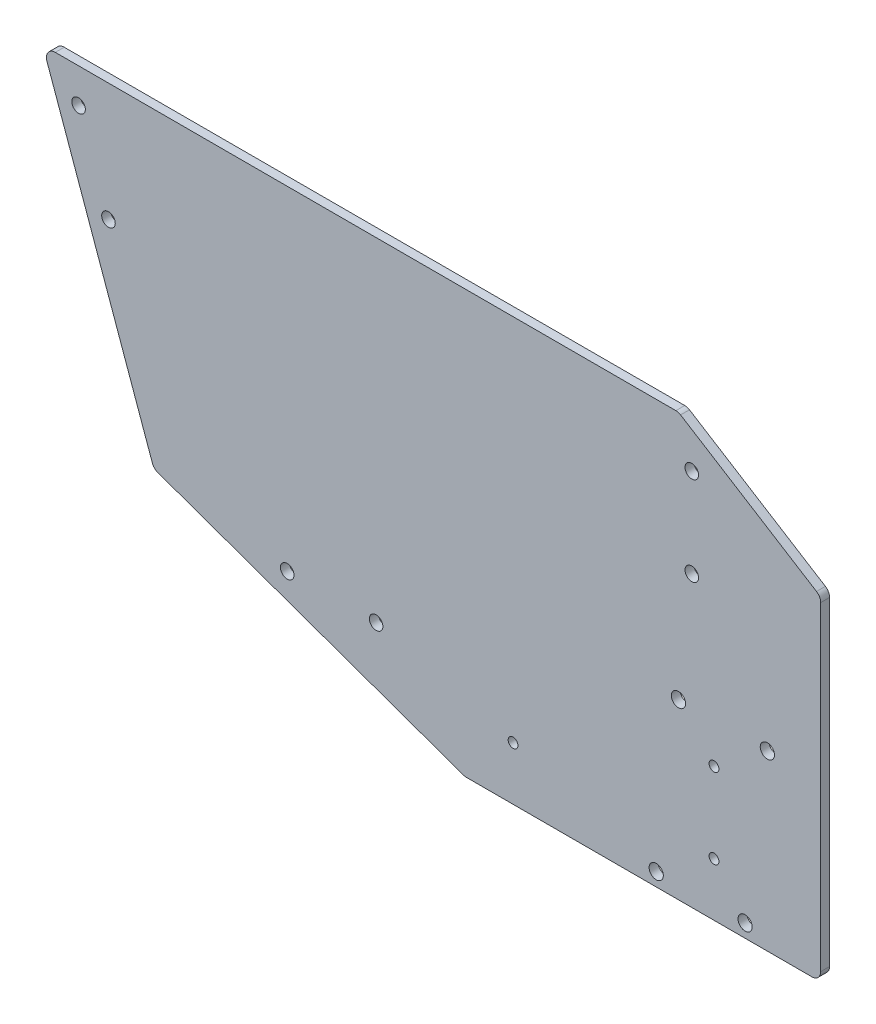
SolidWorks part; units mm, degrees
material "Thornel Mat VMA"
ref_plane "前视基准面" through (0, 0, 0) normal (0, 0, 1) x (1, 0, 0)
ref_plane "上视基准面" through (0, 0, 0) normal (0, 1, 0) x (1, 0, 0)
ref_plane "右视基准面" through (0, 0, 0) normal (1, 0, 0) x (0, 0, -1)
sketch "草图1" plane through (0, 0, 0) normal (0, 0, 1) x (1, 0, 0)
  line L0 (0, 0) -> (0, 75)
  line L1 (0, 75) -> (-32, 95)
  line L2 (-32, 95) -> (-175, 95)
  line L4 (-150, 25) -> (-80, 0)
  line L5 (-80, 0) -> (0, 0)
  line L6 (0, 3) -> (-17, 3) construction
  line L7 (-17, 3) -> (-37, 3) construction
  line L8 (-175, 95) -> (-150, 25)
  line L9 (-175, 95) -> (-170.2913, 96.6817) construction
  line L10 (-170.2913, 96.6817) -> (-166.9279, 87.2643) construction
  line L11 (-166.9279, 87.2643) -> (-160.2012, 68.4294) construction
  line L12 (-32, 95) -> (-29, 95) construction
  line L13 (-29, 95) -> (-29, 85) construction
  line L14 (-29, 85) -> (-29, 65) construction
  line L15 (0, 39) -> (-12, 39) construction
  line L16 (-12, 39) -> (-32, 39) construction
  line L17 (-100, 20) -> (-120, 20) construction
  line L18 (-100, 20) -> (0, 20) construction
  circle A0 centre (-17, 3) radius 1.6
  circle A1 centre (-37, 3) radius 1.6
  circle A2 centre (-166.9279, 87.2643) radius 1.525
  circle A3 centre (-160.2012, 68.4294) radius 1.525
  circle A4 centre (-29, 85) radius 1.525
  circle A5 centre (-29, 65) radius 1.525
  circle A6 centre (-12, 39) radius 1.6
  circle A7 centre (-32, 39) radius 1.6
  circle A8 centre (-120, 20) radius 1.525
  circle A9 centre (-100, 20) radius 1.525
  dimension "D7" = 3.2
  dimension "D15" = 3.05
  dimension "D1" = 75
  dimension "D2" = 80
  dimension "D3" = 95
  dimension "D4" = 70
  dimension "D5" = 25
  dimension "D6" = 150
  dimension "D8" = 3
  dimension "D9" = 20
  dimension "D10" = 17
  dimension "D11" = 32
  dimension "D12" = 5
  dimension "D13" = 10
  dimension "D14" = 20
  dimension "D16" = 3
  dimension "D17" = 10
  dimension "D18" = 20
  dimension "D19" = 39
  dimension "D20" = 20
  dimension "D21" = 100
  dimension "D22" = 20
  dimension "D23" = 12
extrude "凸台-拉伸1" add sketch "草图1" along normal blind 2
sketch "草图4" plane through (0, 0, 0) normal (0, 0, -1) x (-1, 0, 0)
  line L0 (0, 0) -> (0, 75) construction
  line L1 (24, 30) -> (69.2, 30) construction
  line L2 (24, 30) -> (24, 12) construction
  line L3 (24, 12) -> (69.2, 12) construction
  line L4 (69.2, 30) -> (69.2, 12) construction
  line L7 (80, 0) -> (0, 0) construction
  circle A0 centre (24, 30) radius 1.1
  circle A1 centre (24, 12) radius 1.1
  circle A2 centre (69.2, 30) radius 1.1 construction
  circle A3 centre (69.2, 12) radius 1.1
  dimension "D3" = 2.2
  dimension "D1" = 18
  dimension "D2" = 45.2
  dimension "D4" = 12
  dimension "D5" = 24
extrude "切除-拉伸2" cut sketch "草图4" against normal blind 10
sketch "草图5" plane through (0, 0, 0) normal (0, 0, -1) x (-1, 0, 0)
  line L6 (0, 0) -> (80, 0)
  line L7 (80, 0) -> (150, 25)
  line L8 (150, 25) -> (175, 95)
  line L9 (175, 95) -> (32, 95)
  line L10 (32, 95) -> (0, 75)
  line L11 (0, 75) -> (0, 0)
  line L12 (2, 0) -> (79.6536, 0)
  line L13 (80.3262, 0.1165) -> (149.1078, 24.6814)
  line L14 (150.3186, 25.8922) -> (174.0455, 92.3273)
  line L15 (172.162, 95) -> (32.5736, 95)
  line L16 (31.5136, 94.696) -> (0.94, 75.5875)
  line L17 (0, 73.8915) -> (0, 2)
  arc A0 (0.94, 75.5875) -> (0, 73.8915) centre (2, 73.8915) ccw
  arc A1 (32.5736, 95) -> (31.5136, 94.696) centre (32.5736, 93) ccw
  arc A2 (174.0455, 92.3273) -> (172.162, 95) centre (172.162, 93) ccw
  arc A3 (149.1078, 24.6814) -> (150.3186, 25.8922) centre (148.4352, 26.5648) ccw
  arc A4 (79.6536, 0) -> (80.3262, 0.1165) centre (79.6536, 2) ccw
  arc A5 (2, 0) -> (0, 2) centre (2, 2) cw
  dimension "D2" = 2
  dimension "D1" = 0
extrude "切除-拉伸3" cut sketch "草图5" against normal blind 10 flip side to cut
